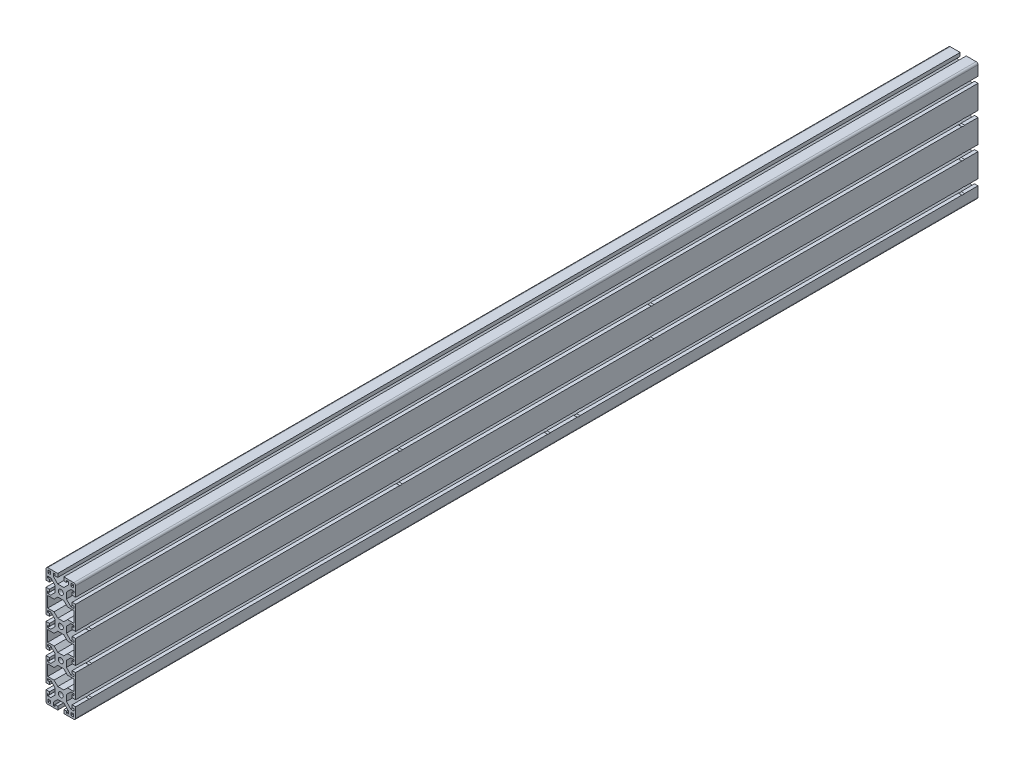
SolidWorks part; units mm, degrees
material "6063-T6"
ref_plane "Front Plane" through (0, 0, 0) normal (0, 0, 1) x (1, 0, 0)
ref_plane "Top Plane" through (0, 0, 0) normal (0, 1, 0) x (1, 0, 0)
ref_plane "Right Plane" through (0, 0, 0) normal (1, 0, 0) x (0, 0, -1)
sketch "Sketch1" plane through (0, 0, 0) normal (0, 1, 0) x (1, 0, 0)
  line L0 (0, 610) -> (0, -610)
  dimension "D1" = 1220
other "40 series TS40-160LM(1)" corner treatment butt1
ref_plane "Plane2" through (0, 0, -610) normal (0, 0, 1) x (1, 0, 0)
sketch "Sketch2" plane through (0, 0, -610) normal (0, 0, 1) x (1, 0, 0)
  line L0 (20, -15.9) -> (20, 15.9)
  line L1 (3.35, 20) -> (7.6, 20) construction
  line L2 (7.6, 24.1) -> (7.6, 15.9)
  line L3 (7.6, 15.9) -> (13.6, 9.9)
  line L4 (13.6, 9.9) -> (17.65, 9.9)
  line L5 (17.65, 9.9) -> (17.65, 12.4)
  line L6 (17.65, 12.4) -> (15.3, 12.4)
  line L7 (15.3, 12.4) -> (15.3, 15.9)
  line L8 (15.3, 15.9) -> (20, 15.9)
  line L9 (22, 0) -> (-22, 0) construction
  line L10 (0, -88) -> (0, 88) construction
  line L11 (0, 16.65) -> (0, 12.4) construction
  line L12 (-4.0632, 12.4) -> (4.0632, 12.4)
  line L13 (4.0632, 12.4) -> (9.0632, 7.4)
  line L14 (9.0632, 7.4) -> (17.65, 7.4)
  line L15 (20, 0) -> (0, 20) construction
  line L16 (17.65, 7.4) -> (17.65, -7.4)
  line L17 (17.65, 0) -> (20, 0) construction
  line L18 (20, 40) -> (0, 20) construction
  line L19 (0, 23.35) -> (0, 27.6) construction
  line L20 (17.65, 40) -> (20, 40) construction
  line L21 (17.65, 32.6) -> (17.65, 47.4)
  line L22 (9.0632, 32.6) -> (17.65, 32.6)
  line L23 (4.0632, 27.6) -> (9.0632, 32.6)
  line L24 (-4.0632, 27.6) -> (4.0632, 27.6)
  line L25 (15.3, 24.1) -> (20, 24.1)
  line L26 (15.3, 27.6) -> (15.3, 24.1)
  line L27 (17.65, 27.6) -> (15.3, 27.6)
  line L28 (17.65, 30.1) -> (17.65, 27.6)
  line L29 (13.6, 30.1) -> (17.65, 30.1)
  line L30 (7.6, 24.1) -> (13.6, 30.1)
  line L31 (20, 55.9) -> (20, 24.1)
  line L32 (0, 56.65) -> (0, 52.4) construction
  line L33 (20, 40) -> (0, 60) construction
  line L34 (20, 80) -> (0, 60) construction
  line L35 (17.5, 80) -> (4.1, 80)
  line L36 (3.35, 60) -> (7.6, 60) construction
  line L37 (7.6, 55.9) -> (13.6, 49.9)
  line L38 (13.6, 49.9) -> (17.65, 49.9)
  line L39 (17.65, 49.9) -> (17.65, 52.4)
  line L40 (17.65, 52.4) -> (15.3, 52.4)
  line L41 (15.3, 52.4) -> (15.3, 55.9)
  line L42 (15.3, 55.9) -> (20, 55.9)
  line L43 (-4.0632, 52.4) -> (4.0632, 52.4)
  line L44 (4.0632, 52.4) -> (9.0632, 47.4)
  line L45 (9.0632, 47.4) -> (17.65, 47.4)
  line L46 (4.1, 75.3) -> (4.1, 80)
  line L47 (7.6, 75.3) -> (4.1, 75.3)
  line L48 (15.3, 64.1) -> (20, 64.1)
  line L49 (15.3, 67.6) -> (15.3, 64.1)
  line L50 (17.65, 67.6) -> (15.3, 67.6)
  line L51 (17.65, 70.1) -> (17.65, 67.6)
  line L52 (13.6, 70.1) -> (17.65, 70.1)
  line L53 (7.6, 64.1) -> (13.6, 70.1)
  line L54 (7.6, 55.9) -> (7.6, 64.1)
  line L55 (20, 77.5) -> (20, 64.1)
  line L56 (7.6, 77.65) -> (7.6, 75.3)
  line L57 (10.1, 77.65) -> (7.6, 77.65)
  line L58 (10.1, 73.6) -> (10.1, 77.65)
  line L59 (4.1, 67.6) -> (10.1, 73.6)
  line L60 (4.1, 67.6) -> (-4.1, 67.6)
  line L61 (-3.35, 60) -> (-7.6, 60) construction
  line L62 (17.5, 77.5) -> (13.7111, 77.5)
  line L63 (17.5, 77.5) -> (17.5, 73.7111)
  line L64 (17.5, 73.7111) -> (13.7111, 73.7111)
  line L65 (13.7111, 77.5) -> (13.7111, 73.7111)
  line L66 (-20, 80) -> (0, 60) construction
  line L67 (-20, 40) -> (0, 60) construction
  line L68 (-17.65, 40) -> (-20, 40) construction
  line L69 (-20, 40) -> (0, 20) construction
  line L70 (-17.65, 0) -> (-20, 0) construction
  line L71 (-20, 0) -> (0, 20) construction
  line L72 (-3.35, 20) -> (-7.6, 20) construction
  line L73 (-13.7111, 77.5) -> (-13.7111, 73.7111)
  line L74 (-17.5, 73.7111) -> (-13.7111, 73.7111)
  line L75 (-17.5, 77.5) -> (-17.5, 73.7111)
  line L76 (-17.5, 77.5) -> (-13.7111, 77.5)
  line L77 (-4.1, 67.6) -> (-10.1, 73.6)
  line L78 (-10.1, 73.6) -> (-10.1, 77.65)
  line L79 (-10.1, 77.65) -> (-7.6, 77.65)
  line L80 (-7.6, 77.65) -> (-7.6, 75.3)
  line L81 (-20, 77.5) -> (-20, 64.1)
  line L82 (-7.6, 55.9) -> (-7.6, 64.1)
  line L83 (-7.6, 64.1) -> (-13.6, 70.1)
  line L84 (-13.6, 70.1) -> (-17.65, 70.1)
  line L85 (-17.65, 70.1) -> (-17.65, 67.6)
  line L86 (-17.65, 67.6) -> (-15.3, 67.6)
  line L87 (-15.3, 67.6) -> (-15.3, 64.1)
  line L88 (-15.3, 64.1) -> (-20, 64.1)
  line L89 (-7.6, 75.3) -> (-4.1, 75.3)
  line L90 (-4.1, 75.3) -> (-4.1, 80)
  line L91 (-9.0632, 47.4) -> (-17.65, 47.4)
  line L92 (-4.0632, 52.4) -> (-9.0632, 47.4)
  line L93 (-15.3, 55.9) -> (-20, 55.9)
  line L94 (-15.3, 52.4) -> (-15.3, 55.9)
  line L95 (-17.65, 52.4) -> (-15.3, 52.4)
  line L96 (-17.65, 49.9) -> (-17.65, 52.4)
  line L97 (-13.6, 49.9) -> (-17.65, 49.9)
  line L98 (-7.6, 55.9) -> (-13.6, 49.9)
  line L99 (-17.5, 80) -> (-4.1, 80)
  line L100 (-20, 55.9) -> (-20, 24.1)
  line L101 (-7.6, 24.1) -> (-13.6, 30.1)
  line L102 (-13.6, 30.1) -> (-17.65, 30.1)
  line L103 (-17.65, 30.1) -> (-17.65, 27.6)
  line L104 (-17.65, 27.6) -> (-15.3, 27.6)
  line L105 (-15.3, 27.6) -> (-15.3, 24.1)
  line L106 (-15.3, 24.1) -> (-20, 24.1)
  line L107 (-4.0632, 27.6) -> (-9.0632, 32.6)
  line L108 (-9.0632, 32.6) -> (-17.65, 32.6)
  line L109 (-17.65, 32.6) -> (-17.65, 47.4)
  line L110 (-17.65, 7.4) -> (-17.65, -7.4)
  line L111 (-9.0632, 7.4) -> (-17.65, 7.4)
  line L112 (-4.0632, 12.4) -> (-9.0632, 7.4)
  line L113 (-15.3, 15.9) -> (-20, 15.9)
  line L114 (-15.3, 12.4) -> (-15.3, 15.9)
  line L115 (-17.65, 12.4) -> (-15.3, 12.4)
  line L116 (-17.65, 9.9) -> (-17.65, 12.4)
  line L117 (-13.6, 9.9) -> (-17.65, 9.9)
  line L118 (-7.6, 15.9) -> (-13.6, 9.9)
  line L119 (-7.6, 24.1) -> (-7.6, 15.9)
  line L120 (-20, -15.9) -> (-20, 15.9)
  line L121 (-3.35, -20) -> (-7.6, -20) construction
  line L122 (-20, 0) -> (0, -20) construction
  line L123 (-20, -40) -> (0, -20) construction
  line L124 (-17.65, -40) -> (-20, -40) construction
  line L125 (-20, -40) -> (0, -60) construction
  line L126 (-20, -80) -> (0, -60) construction
  line L127 (-3.35, -60) -> (-7.6, -60) construction
  line L128 (3.35, -60) -> (7.6, -60) construction
  line L129 (20, -80) -> (0, -60) construction
  line L130 (20, -40) -> (0, -60) construction
  line L131 (0, -56.65) -> (0, -52.4) construction
  line L132 (17.65, -40) -> (20, -40) construction
  line L133 (0, -23.35) -> (0, -27.6) construction
  line L134 (20, -40) -> (0, -20) construction
  line L135 (20, 0) -> (0, -20) construction
  line L136 (0, -16.65) -> (0, -12.4) construction
  line L137 (3.35, -20) -> (7.6, -20) construction
  line L138 (-7.6, -24.1) -> (-7.6, -15.9)
  line L139 (-7.6, -15.9) -> (-13.6, -9.9)
  line L140 (-13.6, -9.9) -> (-17.65, -9.9)
  line L141 (-17.65, -9.9) -> (-17.65, -12.4)
  line L142 (-17.65, -12.4) -> (-15.3, -12.4)
  line L143 (-15.3, -12.4) -> (-15.3, -15.9)
  line L144 (-15.3, -15.9) -> (-20, -15.9)
  line L145 (-4.0632, -12.4) -> (-9.0632, -7.4)
  line L146 (-9.0632, -7.4) -> (-17.65, -7.4)
  line L147 (-17.65, -32.6) -> (-17.65, -47.4)
  line L148 (-9.0632, -32.6) -> (-17.65, -32.6)
  line L149 (-4.0632, -27.6) -> (-9.0632, -32.6)
  line L150 (-15.3, -24.1) -> (-20, -24.1)
  line L151 (-15.3, -27.6) -> (-15.3, -24.1)
  line L152 (-17.65, -27.6) -> (-15.3, -27.6)
  line L153 (-17.65, -30.1) -> (-17.65, -27.6)
  line L154 (-13.6, -30.1) -> (-17.65, -30.1)
  line L155 (-7.6, -24.1) -> (-13.6, -30.1)
  line L156 (-20, -55.9) -> (-20, -24.1)
  line L157 (-17.5, -80) -> (-4.1, -80)
  line L158 (-7.6, -55.9) -> (-13.6, -49.9)
  line L159 (-13.6, -49.9) -> (-17.65, -49.9)
  line L160 (-17.65, -49.9) -> (-17.65, -52.4)
  line L161 (-17.65, -52.4) -> (-15.3, -52.4)
  line L162 (-15.3, -52.4) -> (-15.3, -55.9)
  line L163 (-15.3, -55.9) -> (-20, -55.9)
  line L164 (-4.0632, -52.4) -> (-9.0632, -47.4)
  line L165 (-9.0632, -47.4) -> (-17.65, -47.4)
  line L166 (-4.1, -75.3) -> (-4.1, -80)
  line L167 (-7.6, -75.3) -> (-4.1, -75.3)
  line L168 (-15.3, -64.1) -> (-20, -64.1)
  line L169 (-15.3, -67.6) -> (-15.3, -64.1)
  line L170 (-17.65, -67.6) -> (-15.3, -67.6)
  line L171 (-17.65, -70.1) -> (-17.65, -67.6)
  line L172 (-13.6, -70.1) -> (-17.65, -70.1)
  line L173 (-7.6, -64.1) -> (-13.6, -70.1)
  line L174 (-7.6, -55.9) -> (-7.6, -64.1)
  line L175 (-20, -77.5) -> (-20, -64.1)
  line L176 (-7.6, -77.65) -> (-7.6, -75.3)
  line L177 (-10.1, -77.65) -> (-7.6, -77.65)
  line L178 (-10.1, -73.6) -> (-10.1, -77.65)
  line L179 (-4.1, -67.6) -> (-10.1, -73.6)
  line L180 (-17.5, -77.5) -> (-13.7111, -77.5)
  line L181 (-17.5, -77.5) -> (-17.5, -73.7111)
  line L182 (-17.5, -73.7111) -> (-13.7111, -73.7111)
  line L183 (-13.7111, -77.5) -> (-13.7111, -73.7111)
  line L184 (13.7111, -77.5) -> (13.7111, -73.7111)
  line L185 (17.5, -73.7111) -> (13.7111, -73.7111)
  line L186 (17.5, -77.5) -> (17.5, -73.7111)
  line L187 (17.5, -77.5) -> (13.7111, -77.5)
  line L188 (4.1, -67.6) -> (-4.1, -67.6)
  line L189 (4.1, -67.6) -> (10.1, -73.6)
  line L190 (10.1, -73.6) -> (10.1, -77.65)
  line L191 (10.1, -77.65) -> (7.6, -77.65)
  line L192 (7.6, -77.65) -> (7.6, -75.3)
  line L193 (20, -77.5) -> (20, -64.1)
  line L194 (7.6, -55.9) -> (7.6, -64.1)
  line L195 (7.6, -64.1) -> (13.6, -70.1)
  line L196 (13.6, -70.1) -> (17.65, -70.1)
  line L197 (17.65, -70.1) -> (17.65, -67.6)
  line L198 (17.65, -67.6) -> (15.3, -67.6)
  line L199 (15.3, -67.6) -> (15.3, -64.1)
  line L200 (15.3, -64.1) -> (20, -64.1)
  line L201 (7.6, -75.3) -> (4.1, -75.3)
  line L202 (4.1, -75.3) -> (4.1, -80)
  line L203 (9.0632, -47.4) -> (17.65, -47.4)
  line L204 (4.0632, -52.4) -> (9.0632, -47.4)
  line L205 (-4.0632, -52.4) -> (4.0632, -52.4)
  line L206 (15.3, -55.9) -> (20, -55.9)
  line L207 (15.3, -52.4) -> (15.3, -55.9)
  line L208 (17.65, -52.4) -> (15.3, -52.4)
  line L209 (17.65, -49.9) -> (17.65, -52.4)
  line L210 (13.6, -49.9) -> (17.65, -49.9)
  line L211 (7.6, -55.9) -> (13.6, -49.9)
  line L212 (17.5, -80) -> (4.1, -80)
  line L213 (20, -55.9) -> (20, -24.1)
  line L214 (7.6, -24.1) -> (13.6, -30.1)
  line L215 (13.6, -30.1) -> (17.65, -30.1)
  line L216 (17.65, -30.1) -> (17.65, -27.6)
  line L217 (17.65, -27.6) -> (15.3, -27.6)
  line L218 (15.3, -27.6) -> (15.3, -24.1)
  line L219 (15.3, -24.1) -> (20, -24.1)
  line L220 (-4.0632, -27.6) -> (4.0632, -27.6)
  line L221 (4.0632, -27.6) -> (9.0632, -32.6)
  line L222 (9.0632, -32.6) -> (17.65, -32.6)
  line L223 (17.65, -32.6) -> (17.65, -47.4)
  line L224 (9.0632, -7.4) -> (17.65, -7.4)
  line L225 (4.0632, -12.4) -> (9.0632, -7.4)
  line L226 (-4.0632, -12.4) -> (4.0632, -12.4)
  line L227 (15.3, -15.9) -> (20, -15.9)
  line L228 (15.3, -12.4) -> (15.3, -15.9)
  line L229 (17.65, -12.4) -> (15.3, -12.4)
  line L230 (17.65, -9.9) -> (17.65, -12.4)
  line L231 (13.6, -9.9) -> (17.65, -9.9)
  line L232 (7.6, -15.9) -> (13.6, -9.9)
  line L233 (7.6, -24.1) -> (7.6, -15.9)
  arc A0 (0, 56.65) -> (0, 63.35) centre (0, 60) ccw
  circle A1 centre (0, 20) radius 3.35
  arc A2 (17.5, 80) -> (20, 77.5) centre (17.5, 77.5) cw
  arc A3 (-17.5, 80) -> (-20, 77.5) centre (-17.5, 77.5) ccw
  arc A4 (0, 56.65) -> (0, 63.35) centre (0, 60) cw
  arc A5 (0, -56.65) -> (0, -63.35) centre (0, -60) ccw
  arc A6 (-17.5, -80) -> (-20, -77.5) centre (-17.5, -77.5) cw
  arc A7 (17.5, -80) -> (20, -77.5) centre (17.5, -77.5) ccw
  circle A8 centre (0, -20) radius 3.35
  arc A9 (0, -56.65) -> (0, -63.35) centre (0, -60) cw
  point P19 (17.65, 15.9)
  point P27 (0, -80)
  point P42 (-20, -60)
  point P43 (20, -80)
  point P94 (0, 67.6)
  point P262 (0, -67.6)
  point P263 (-20, -80)
  point P264 (20, -60)
  point P265 (0, -60)
  point P266 (0, -40)
  point P267 (20, -40)
  point P268 (-20, -20)
  point P269 (-20, -40)
  point P270 (20, -20)
  point P271 (0, -20)
  point P272 (0, 0)
  point P273 (20, 0)
  point P274 (-20, 20)
  point P275 (-20, 0)
  point P276 (20, 20)
  point P277 (0, 20)
  point P278 (0, 40)
  point P279 (20, 40)
  point P280 (20, 60)
  point P281 (-20, 40)
  point P282 (-20, 60)
  point P283 (0, 60)
  point P284 (0, 80)
  point P285 (-20, 80)
  point P286 (0, 0)
  point P287 (20, 80)
  dimension "D2" = 4.1
  dimension "D4" = 20
  dimension "D9" = 2.5
  dimension "D3" = 3.35
  dimension "D5" = 2.5
  dimension "D10" = 20
  dimension "D6" = 10.1
  dimension "D8" = 12.4
  dimension "D11" = 2.5
  dimension "D7" = 4.7
hole_wizard "M8 Clearance Hole1" positions "Sketch3" profile "Sketch4" hole size "M8" standard "ANSI Metric" end condition through all
sketch "Sketch3" plane through (20, 0, 0) normal (1, 0, 0) x (0, 0, -1)
  line L1 (-590, 20) -> (590, 20)
  line L2 (-590, 20) -> (-590, -20)
  line L3 (-590, -20) -> (590, -20)
  line L4 (590, 20) -> (590, -20)
  line L5 (22, 0) -> (-22, 0) construction
  line L6 (610, -15.9) -> (610, 15.9) construction
  line L7 (-610, -15.9) -> (-610, 15.9) construction
  line L8 (-170, 20) -> (-170, -20)
  line L11 (170, 20) -> (170, -20)
  line L12 (-590, -20) -> (-590, -60)
  line L14 (590, -20) -> (590, -60)
  point P1 (-590, 20)
  point P2 (590, -20)
  point P399 (-590, -20)
  point P400 (590, 20)
  point P401 (590, 0)
  point P408 (-170, 20)
  point P409 (-170, -20)
  point P413 (170, 20)
  point P414 (170, -20)
  point P425 (-590, -60)
  point P435 (590, -60)
  dimension "D1" = 40
  dimension "D2" = 20
  dimension "D3" = 20
  dimension "D4" = 170
  dimension "D5" = 170
  dimension "D6" = 420
sketch "Sketch4" plane through (20, 20, 590) normal (0, 1, 0) x (0, 0, -1)
  line L0 (0, 0) -> (0, 40)
  line L1 (0, 40) -> (4.5, 40)
  line L2 (4.5, 40) -> (4.5, 0)
  line L5 (4.5, 0) -> (0, 0)
  line L11 (0, -6.35) -> (0, 107.95) construction
  dimension "Thru Hole Dia." = 9
  dimension "Thru Hole Depth" = 40
hole_wizard "M8 Clearance Hole3" [suppressed] positions "Sketch14" profile "Sketch15" hole size "M8" standard "ANSI Metric"
sketch "Sketch14" plane through (20, 0, 0) normal (1, 0, 0) x (0, 0, -1)
  line L0 (-420, 20) -> (-420, -20)
  line L1 (-840, 20) -> (840, 20) construction
  line L2 (-840, -20) -> (840, -20) construction
  line L5 (-840, 20) -> (-840, -20) construction
  line L6 (420, 20) -> (420, -20)
  line L8 (840, 20) -> (840, -20) construction
  point P31 (-420, 20)
  point P32 (-420, -20)
  point P43 (420, 20)
  point P44 (420, -20)
  dimension "D1" = 420
  dimension "D2" = 420
sketch "Sketch15" plane through (20, 20, 420) normal (0, 1, 0) x (0, 0, -1)
  line L0 (0, 0) -> (0, 40)
  line L1 (0, 40) -> (4.5, 40)
  line L2 (4.5, 40) -> (4.5, 0)
  line L5 (4.5, 0) -> (0, 0)
  line L11 (0, -6.35) -> (0, 107.95) construction
  dimension "Thru Hole Dia." = 9
  dimension "Thru Hole Depth" = 40
hole_wizard "M8 Clearance Hole2" positions "Sketch5" profile "Sketch6" hole size "M8" standard "ANSI Metric" end condition through all
sketch "Sketch5" plane through (20, 0, 0) normal (1, 0, 0) x (0, 0, -1)
  line L0 (30, -60) -> (70, -60)
  point P1 (30, -60)
  point P2 (70, -60)
  point P4 (50, -60)
  dimension "D1" = 50
  dimension "D2" = 40
  dimension "D3" = 60
sketch "Sketch6" plane through (20, -60, -30) normal (0, 1, 0) x (0, 0, -1)
  line L0 (0, 0) -> (0, 40)
  line L1 (0, 40) -> (4.5, 40)
  line L2 (4.5, 40) -> (4.5, 0)
  line L5 (4.5, 0) -> (0, 0)
  line L11 (0, -6.35) -> (0, 107.95) construction
  dimension "Thru Hole Dia." = 9
  dimension "Thru Hole Depth" = 40
hole_wizard "M8x1.25 Tapped Hole2" positions "Sketch10" profile "Sketch11" tap size "M8x1.25" standard "ANSI Metric"
sketch "Sketch10" plane through (0, 0, 610) normal (0, 0, 1) x (1, 0, 0)
  point P0 (0, 60)
  point P3 (0, 20)
  point P6 (0, -20)
sketch "Sketch11" plane through (0, 60, 610) normal (1, 0, 0) x (0, -1, 0)
  line L0 (0, 0) -> (0, 25.7929)
  line L1 (0, 25.7929) -> (3.4, 23.75)
  line L2 (3.4, 23.75) -> (3.4, 0)
  line L5 (3.4, 0) -> (0, 0)
  line L10 (0, 25.7929) -> (-3.4, 23.75) construction
  line L11 (0, -6.35) -> (0, 107.95) construction
  dimension "Tap Drill Dia." = 6.8
  dimension "Tap Drill Depth" = 23.75
  dimension "Drill Angle" = 118
cosmetic thread "Hole Thread1" parameters "D1"=20, "D2"=8
cosmetic thread "Hole Thread2" parameters "D1"=20, "D2"=8
cosmetic thread "Hole Thread3" parameters "D1"=20, "D2"=8
hole_wizard "M8x1.25 Tapped Hole3" positions "Sketch12" profile "Sketch13" tap size "M8x1.25" standard "ANSI Metric"
sketch "Sketch12" plane through (0, 0, -610) normal (0, 0, -1) x (-1, 0, 0)
  point P0 (0, 60)
  point P3 (0, 20)
  point P6 (0, -20)
  point P9 (0, -60)
sketch "Sketch13" plane through (0, 60, -610) normal (1, 0, 0) x (0, 1, 0)
  line L0 (0, 0) -> (0, 25.7929)
  line L1 (0, 25.7929) -> (3.4, 23.75)
  line L2 (3.4, 23.75) -> (3.4, 0)
  line L5 (3.4, 0) -> (0, 0)
  line L10 (0, 25.7929) -> (-3.4, 23.75) construction
  line L11 (0, -6.35) -> (0, 107.95) construction
  dimension "Tap Drill Dia." = 6.8
  dimension "Tap Drill Depth" = 23.75
  dimension "Drill Angle" = 118
cosmetic thread "Hole Thread4" parameters "D1"=20, "D2"=8
cosmetic thread "Hole Thread5" parameters "D1"=20, "D2"=8
cosmetic thread "Hole Thread6" parameters "D1"=20, "D2"=8
cosmetic thread "Hole Thread7" parameters "D1"=20, "D2"=8
